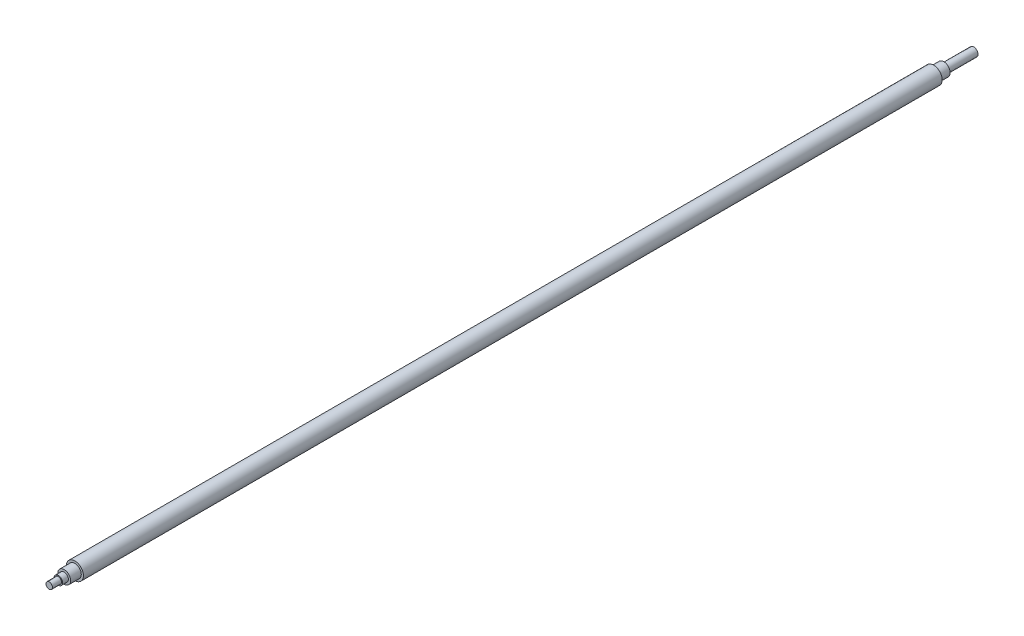
SolidWorks part; units mm, degrees
ref_plane "Piano frontale" through (0, 0, 0) normal (0, 0, 1) x (1, 0, 0)
ref_plane "Piano superiore" through (0, 0, 0) normal (0, 1, 0) x (1, 0, 0)
ref_plane "Piano destro" through (0, 0, 0) normal (1, 0, 0) x (0, 0, -1)
sketch "Schizzo2" plane through (0, 0, 0) normal (1, 0, 0) x (0, 0, -1)
  line L0 (0, 0) -> (0, 3)
  line L1 (0, 3) -> (8.5, 3)
  line L2 (8.5, 3) -> (8.5, 4)
  line L3 (8.5, 4) -> (14, 4)
  line L4 (14, 4) -> (14, 6)
  line L5 (14, 6) -> (24, 6)
  line L6 (24, 6) -> (24, 8)
  line L7 (24, 8) -> (827, 8)
  line L8 (827, 8) -> (827, 6)
  line L9 (827, 6) -> (836.5, 6)
  line L10 (836.5, 6) -> (836.5, 4)
  line L11 (864.5, 0) -> (0, 0)
  line L14 (864.5, 0) -> (864.5, 4)
  line L15 (0, 0) -> (351.0218, 0) construction
  line L18 (836.5, 4) -> (864.5, 4)
  point P33 (0, 0)
  dimension "D2" = 6
  dimension "D3" = 8
  dimension "D4" = 12
  dimension "D5" = 16
  dimension "D6" = 12
  dimension "D7" = 8
  dimension "D8" = 8.5
  dimension "D9" = 5.5
  dimension "D10" = 10
  dimension "D11" = 803
  dimension "D12" = 9.5
  dimension "D13" = 28
  dimension "D14" = 864.5
revolve "Rivoluzione2" add sketch "Schizzo2" angle 360 about L15
